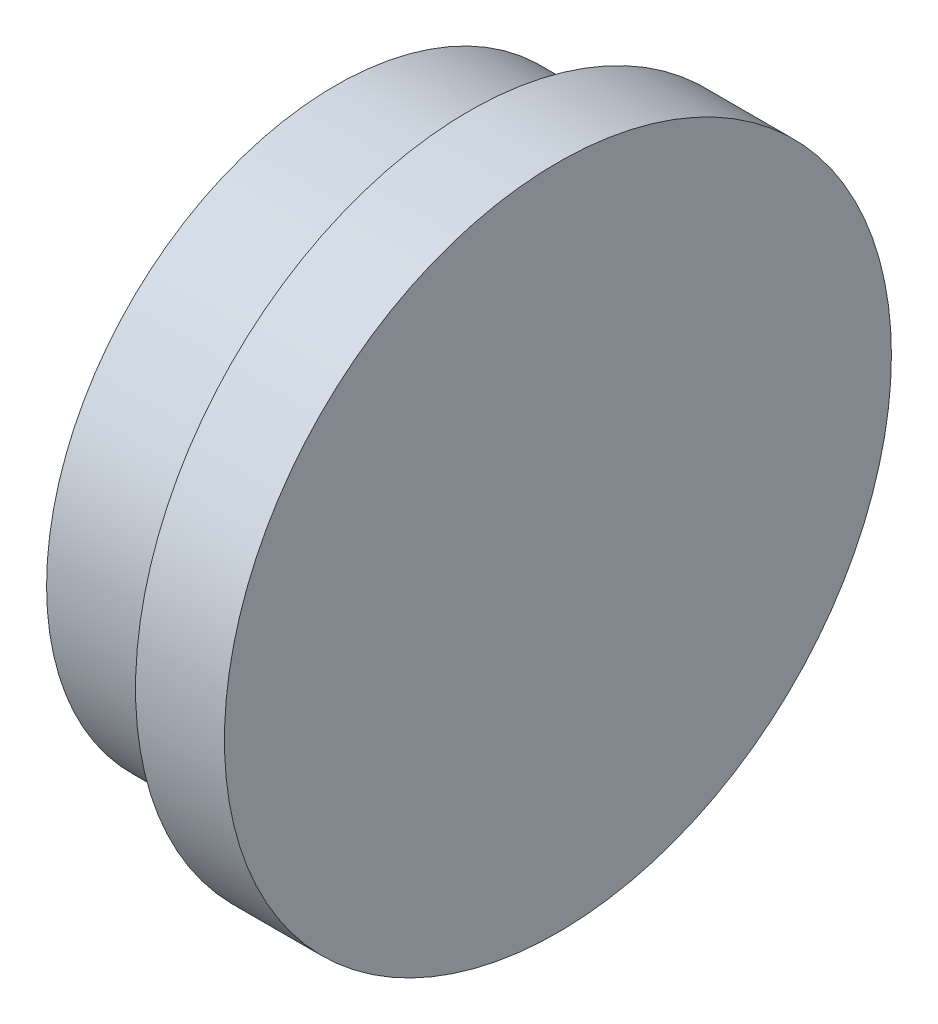
SolidWorks part; units mm, degrees
ref_plane "前视基准面" through (0, 0, 0) normal (0, 0, 1) x (1, 0, 0)
ref_plane "上视基准面" through (0, 0, 0) normal (0, 1, 0) x (1, 0, 0)
ref_plane "右视基准面" through (0, 0, 0) normal (1, 0, 0) x (0, 0, -1)
sketch "草图1" plane through (0, 0, 0) normal (1, 0, 0) x (0, 0, -1)
  circle A0 centre (0, 0) radius 16.51
extrude "凸台-拉伸1" add sketch "草图1" along normal blind 7.62
sketch "草图2" plane through (7.62, 0, 0) normal (1, 0, 0) x (0, 0, -1)
  circle A0 centre (0, 0) radius 19.05
extrude "凸台-拉伸2" add sketch "草图2" along normal blind 5.08
ref_axis "基准轴1" through (0, 20.955, 0) along (0, -1, 0)
ref_plane "基准面1" through (0, 0, 0) normal (0, 1, 0) x (1, 0, 0)
